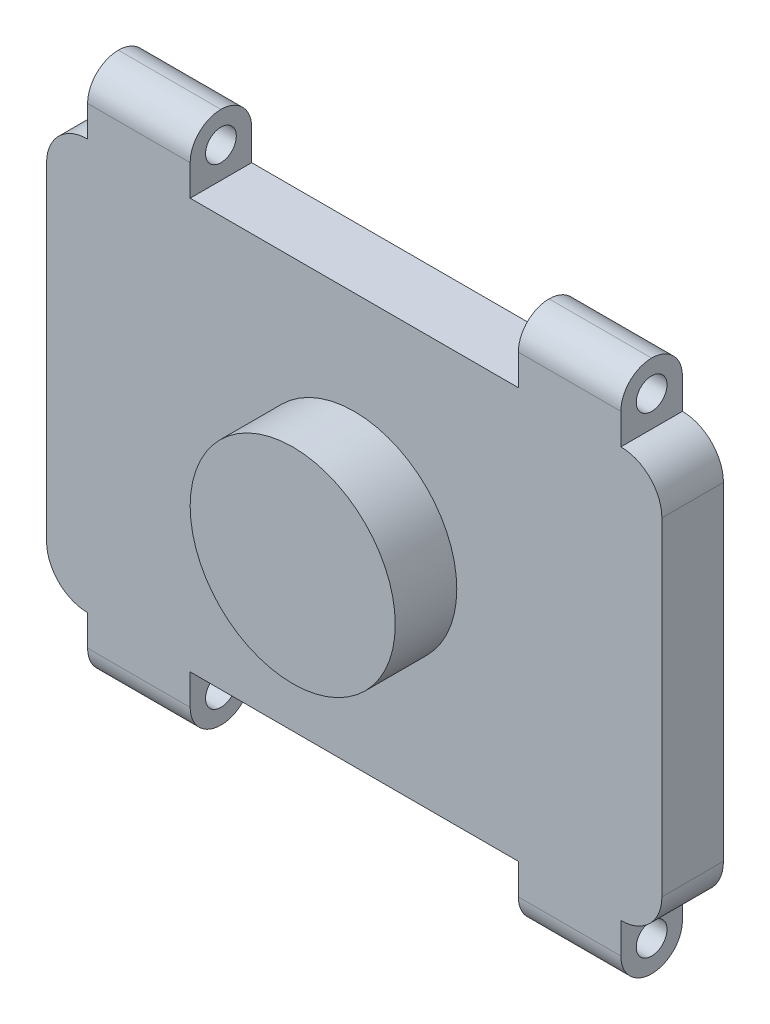
SolidWorks part; units mm, degrees
ref_plane "Ön Düzlem" through (0, 0, 0) normal (0, 0, 1) x (1, 0, 0)
ref_plane "Üst Düzlem" through (0, 0, 0) normal (0, 1, 0) x (1, 0, 0)
ref_plane "Sağ Düzlem" through (0, 0, 0) normal (1, 0, 0) x (0, 0, -1)
sketch "Çizim1" plane through (0, 0, 0) normal (0, 0, 1) x (1, 0, 0)
  line L1 (-1654.8474, 870.6468) -> (1345.1526, 870.6468)
  line L2 (-1654.8474, 870.6468) -> (-1654.8474, -1129.3532)
  line L3 (-1654.8474, -1129.3532) -> (1345.1526, -1129.3532)
  line L4 (1345.1526, 870.6468) -> (1345.1526, -1129.3532)
  dimension "D1" = 2000
  dimension "D2" = 3000
extrude "Yükseklik-Ekstrüzyon1" add sketch "Çizim1" along normal blind 300
fillet "Radyus1" radius 200 4 edges at (-1654.8474, -1129.3532, 150) (1345.1526, -1129.3532, 150) (1345.1526, 870.6468, 150) (-1654.8474, 870.6468, 150)
sketch "Çizim2" plane through (0, 0, 300) normal (0, 0, 1) x (1, 0, 0)
  line L1 (-1454.8474, 870.6468) -> (-954.8474, 870.6468)
  line L2 (-1454.8474, 870.6468) -> (-1454.8474, 1170.6468)
  line L3 (-1454.8474, 1170.6468) -> (-954.8474, 1170.6468)
  line L4 (-954.8474, 870.6468) -> (-954.8474, 1170.6468)
  line L6 (645.1526, 870.6468) -> (645.1526, 1170.6468)
  line L7 (1145.1526, 1170.6468) -> (645.1526, 1170.6468)
  line L8 (1145.1526, 870.6468) -> (1145.1526, 1170.6468)
  line L9 (1145.1526, 870.6468) -> (645.1526, 870.6468)
  line L12 (1145.1526, -1129.3532) -> (645.1526, -1129.3532)
  line L13 (1145.1526, -1129.3532) -> (1145.1526, -1429.3532)
  line L14 (1145.1526, -1429.3532) -> (645.1526, -1429.3532)
  line L15 (645.1526, -1129.3532) -> (645.1526, -1429.3532)
  line L16 (-954.8474, -1129.3532) -> (-954.8474, -1429.3532)
  line L17 (-1454.8474, -1429.3532) -> (-954.8474, -1429.3532)
  line L18 (-1454.8474, -1129.3532) -> (-1454.8474, -1429.3532)
  line L19 (-1454.8474, -1129.3532) -> (-954.8474, -1129.3532)
  dimension "D1" = 300
  dimension "D2" = 500
extrude "Yükseklik-Ekstrüzyon2" add sketch "Çizim2" against normal blind 300
sketch "Çizim3" plane through (1345.1526, 0, 0) normal (1, 0, 0) x (0, 0, -1)
  circle A0 centre (-150, 1020.6468) radius 75
  circle A1 centre (-150, -1279.3532) radius 75
extrude "Kes-Ekstrüzyon1" cut sketch "Çizim3" against normal blind 3686
fillet "Radyus2" radius 150 8 edges at (-1204.8474, -1429.3532, 0) (-1204.8474, -1429.3532, 300) (895.1526, -1429.3532, 0) (895.1526, -1429.3532, 300) (895.1526, 1170.6468, 0) (895.1526, 1170.6468, 300) (-1204.8474, 1170.6468, 0) (-1204.8474, 1170.6468, 300)
sketch "Çizim4" plane through (0, 0, 300) normal (0, 0, 1) x (1, 0, 0)
  circle A0 centre (-154.8474, -129.3532) radius 500
extrude "Yükseklik-Ekstrüzyon3" add sketch "Çizim4" along normal blind 300
